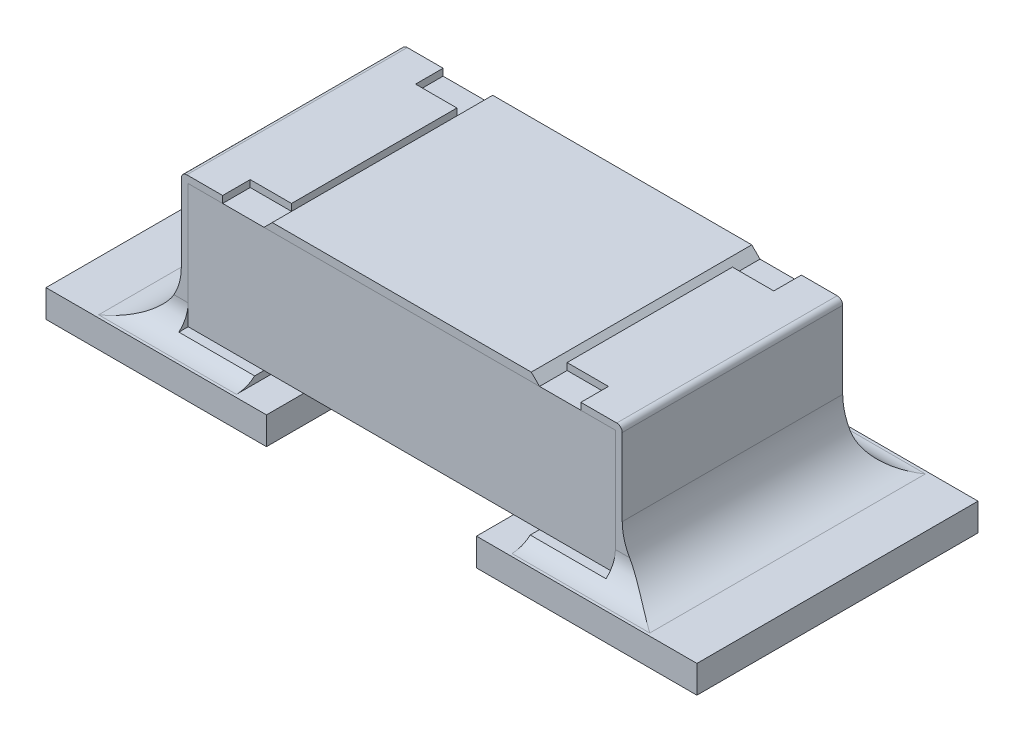
SolidWorks part; units mm, degrees
material "Ceramic Porcelain"
ref_plane "Front Plane" through (0, 0, 0) normal (0, 0, 1) x (1, 0, 0)
ref_plane "Top Plane" through (0, 0, 0) normal (0, 1, 0) x (1, 0, 0)
ref_plane "Right Plane" through (0, 0, 0) normal (1, 0, 0) x (0, 0, -1)
sketch "Sketch1" plane through (0, 0, 0) normal (1, 0, 0) x (0, 0, -1)
  line L0 (0, 55) -> (0, -55) construction
  line L1 (-0.4, 0.575) -> (0.4, 0.575)
  line L2 (-0.4, 0.575) -> (-0.4, 0.125)
  line L3 (-0.4, 0.125) -> (0.4, 0.125)
  line L4 (0.4, 0.575) -> (0.4, 0.125)
  line L5 (55, 0) -> (-55, 0) construction
  dimension "D1" = 0.8
  dimension "D2" = 0.4
  dimension "D3" = 0.45
  dimension "D4" = 0.125
extrude "Boss-Extrude1" add sketch "Sketch1" along normal mid plane 1.55
sketch "Sketch2" plane through (0, 0, 0) normal (0, 0, 1) x (1, 0, 0)
  line L0 (-0.5, 0.6) -> (-0.78, 0.6)
  line L1 (-0.8, 0.58) -> (-0.8, 0.1)
  line L2 (-0.8, 0.1) -> (-0.5, 0.1)
  line L3 (-0.5, 0.1) -> (-0.5, 0.125)
  line L4 (0.775, 0.125) -> (-0.775, 0.125) construction
  line L5 (-0.5, 0.125) -> (-0.775, 0.125)
  line L6 (-0.775, 0.125) -> (-0.775, 0.575)
  line L7 (-0.775, 0.575) -> (-0.5, 0.575)
  line L8 (0.775, 0.575) -> (-0.775, 0.575) construction
  line L9 (-0.5, 0.575) -> (-0.5, 0.6)
  line L11 (0.5, 0.575) -> (0.5, 0.6)
  line L12 (0.5, 0.6) -> (0.78, 0.6)
  line L13 (0.8, 0.58) -> (0.8, 0.1)
  line L14 (0.8, 0.1) -> (0.5, 0.1)
  line L15 (0.5, 0.1) -> (0.5, 0.125)
  line L16 (0.5, 0.125) -> (0.775, 0.125)
  line L17 (0.775, 0.125) -> (0.775, 0.575)
  line L18 (0.775, 0.575) -> (0.5, 0.575)
  arc A0 (0.78, 0.6) -> (0.8, 0.58) centre (0.78, 0.58) cw
  arc A1 (-0.78, 0.6) -> (-0.8, 0.58) centre (-0.78, 0.58) ccw
  point P28 (-0.8, 0.6)
  dimension "D6" = 0.02
  dimension "D1" = 0.025
  dimension "D2" = 0.025
  dimension "D3" = 0.025
  dimension "D4" = 0.3
  dimension "D5" = 0.3
extrude "Boss-Extrude2" add sketch "Sketch2" along normal mid plane 0.8 separate body
sketch "Sketch3" plane through (0, 0.6, 0) normal (0, 1, 0) x (1, 0, 0)
  line L0 (0.5, -0.4) -> (0.5, 0.4) construction
  line L1 (-0.5, 0.4) -> (-0.65, 0.4)
  line L2 (-0.5, 0.4) -> (-0.5, 0.3)
  line L3 (-0.5, 0.3) -> (-0.65, 0.3)
  line L4 (-0.65, 0.4) -> (-0.65, 0.3)
  line L5 (-0.5, -0.4) -> (-0.65, -0.4)
  line L6 (-0.5, -0.4) -> (-0.5, -0.3)
  line L7 (-0.5, -0.3) -> (-0.65, -0.3)
  line L8 (-0.65, -0.4) -> (-0.65, -0.3)
  line L9 (0.5, -0.4) -> (0.65, -0.4)
  line L10 (0.5, -0.4) -> (0.5, -0.3)
  line L11 (0.5, -0.3) -> (0.65, -0.3)
  line L12 (0.65, -0.4) -> (0.65, -0.3)
  line L13 (0.775, -0.4) -> (-0.775, -0.4) construction
  line L15 (0.5, 0.4) -> (0.65, 0.4)
  line L16 (0.5, 0.4) -> (0.5, 0.3)
  line L17 (0.5, 0.3) -> (0.65, 0.3)
  line L18 (0.65, 0.4) -> (0.65, 0.3)
  dimension "D1" = 0.15
  dimension "D2" = 0.1
extrude "Cut-Extrude1" cut sketch "Sketch3" against normal blind 0.025
sketch "Sketch4" plane through (0, 0, 0) normal (0, 0, 1) x (1, 0, 0)
  line L0 (-0.5, 0.575) -> (0.5, 0.575)
  line L1 (0.5, 0.575) -> (0.47, 0.605)
  line L2 (0.47, 0.605) -> (-0.47, 0.605)
  line L3 (-0.47, 0.605) -> (-0.5, 0.575)
  dimension "D1" = 45
  dimension "D2" = 45
  dimension "D3" = 0.03
extrude "Boss-Extrude3" add sketch "Sketch4" along normal mid plane 0.8 separate body
sketch "Sketch7" plane through (0, 0, 0) normal (0, 1, 0) x (1, 0, 0)
  line L0 (0, -0.2833) -> (0, 0.2833) construction
  line L1 (-0.381, -0.51) -> (-1.181, -0.51)
  line L2 (-0.381, -0.51) -> (-0.381, 0.51)
  line L3 (-0.381, 0.51) -> (-1.181, 0.51)
  line L4 (-1.181, -0.51) -> (-1.181, 0.51)
  line L5 (0.381, -0.51) -> (1.181, -0.51)
  line L6 (0.381, -0.51) -> (0.381, 0.51)
  line L7 (0.381, 0.51) -> (1.181, 0.51)
  line L8 (1.181, -0.51) -> (1.181, 0.51)
  line L9 (-0.2833, 0) -> (0.2833, 0) construction
  dimension "D1" = 0.8
  dimension "D2" = 0.381
  dimension "D3" = 0.381
  dimension "D4" = 1.02
  dimension "D5" = 0.51
extrude "Boss-Extrude5" add sketch "Sketch7" along normal blind 0.1
fillet "Fillet3" radius 0.2 1 edges at (-0.8, 0.1, 0)
fillet "Fillet4" radius 0.2 1 edges at (0.8, 0.1, 0)
fillet "Fillet5" radius 0.1 2 edges at (0.75, 0.1, -0.4) (0.75, 0.1, 0.4)
fillet "Fillet6" radius 0.1 2 edges at (-0.75, 0.1, 0.4) (-0.75, 0.1, -0.4)
